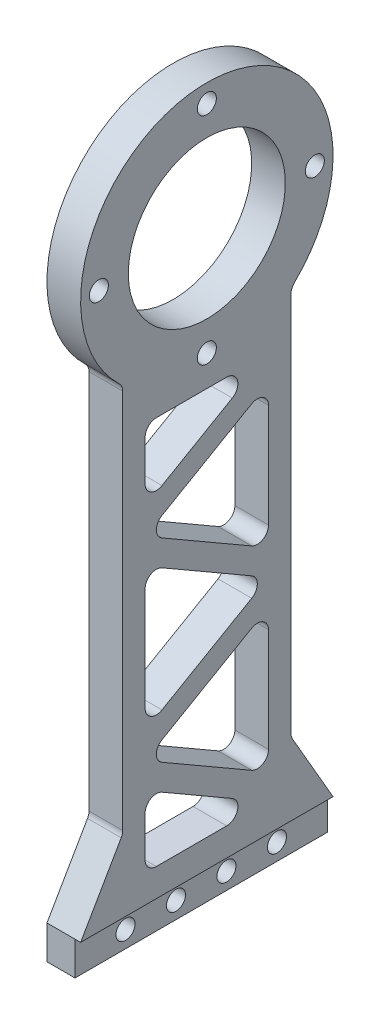
SolidWorks part; units mm, degrees
material "Сплав 2024"
ref_plane "Спереди" through (0, 0, 0) normal (0, 0, 1) x (1, 0, 0)
ref_plane "Сверху" through (0, 0, 0) normal (0, 1, 0) x (1, 0, 0)
ref_plane "Справа" through (0, 0, 0) normal (1, 0, 0) x (0, 0, -1)
sketch "Эскиз1" plane through (0, 0, 0) normal (0, 1, 0) x (1, 0, 0)
  line L1 (0, 0) -> (6, 0)
  line L2 (0, 0) -> (0, -30)
  line L3 (0, -30) -> (6, -30)
  line L4 (6, 0) -> (6, -30)
  dimension "D1" = 6
  dimension "D2" = 30
extrude "Бобышка-Вытянуть1" add sketch "Эскиз1" along normal blind 227
sketch "Эскиз2" plane through (0, 0, 0) normal (-1, 0, 0) x (0, 0, 1)
  line L0 (30, 105) -> (0, 105) construction
  line L3 (15, 227) -> (15, 0) construction
  line L4 (0, 227) -> (30, 227) construction
  line L5 (0, 0) -> (30, 0) construction
  line L6 (30, 0) -> (0, 0) construction
  circle A0 centre (15, 105) radius 22.5
  dimension "D1" = 45
  dimension "D2" = 105
extrude "Бобышка-Вытянуть2" add sketch "Эскиз2" against normal up to surface (6 mm away) up to face at (6, 113.5, 15)
sketch "Эскиз3" plane through (0, 0, 0) normal (-1, 0, 0) x (0, 0, 1)
  circle A0 centre (15, 105) radius 14
  dimension "D1" = 28
extrude "Вырез-Вытянуть1" cut sketch "Эскиз3" against normal through all
sketch "Эскиз4" plane through (6, 0, 0) normal (-1, 0, 0) x (0, 0, 1)
  line L0 (15, 127.5) -> (15, 82.5) construction
  line L1 (15, 227) -> (15, 0) construction
  line L2 (37.5, 105) -> (-7.5, 105) construction
  circle A0 centre (15, 105) radius 19.25 construction
  circle A1 centre (15, 105) radius 22.5 construction
  dimension "D1" = 38.5
hole_wizard "Отверстие с зазором M32" positions "Эскиз6" profile "Эскиз5" hole size "M3" standard "Ansi Metric" end condition through all
sketch "Эскиз6" plane through (6, -25.0247, 7.2629) normal (-1, 0, 0) x (0, 0, 1)
  line L0 (7.7371, 152.5247) -> (7.7371, 107.5247) construction
  line L1 (30.2371, 130.0247) -> (-14.7629, 130.0247) construction
  circle A0 centre (7.7371, 130.0247) radius 19.25 construction
  point P0 (7.7371, 149.2747)
  point P6 (-11.5129, 130.0247)
  point P10 (7.7371, 110.7747)
  point P12 (26.9871, 130.0247)
sketch "Эскиз5" plane through (6, 124.25, 15) normal (0, 1, 0) x (0, 0, -1)
  line L0 (0, 0) -> (0, 6)
  line L1 (0, 6) -> (1.7, 6)
  line L2 (1.7, 6) -> (1.7, 0)
  line L5 (1.7, 0) -> (0, 0)
  line L11 (0, -6.35) -> (0, 107.95) construction
  dimension "Диаметр сквозного отверстия" = 3.4
  dimension "Глубина сквозного отверстия" = 6
sketch "Эскиз8" plane through (6, 0, 0) normal (1, 0, 0) x (0, 0, -1)
  line L0 (-15, 227) -> (-15, 0) construction
  line L1 (-30, 227) -> (0, 227) construction
  line L2 (-30, 0) -> (0, 0) construction
  line L3 (19.447, 105) -> (-49.447, 105) construction
  line L4 (0, 227) -> (0, 121.7705) construction
  line L5 (-26, 145) -> (-4, 145) construction
  line L6 (-26, 145) -> (-26, 65) construction
  line L7 (-26, 65) -> (-4, 65) construction
  line L8 (-4, 145) -> (-4, 65) construction
  line L9 (-26, 145) -> (-4, 65) construction
  line L10 (-26, 65) -> (-4, 145) construction
  point P8 (-15, 105)
  point P9 (-15, 105)
  dimension "D1" = 4
  dimension "D2" = 80
  dimension "D3" = 105
sketch "Эскиз11" plane through (6, 0, 0) normal (1, 0, 0) x (0, 0, -1)
  line L0 (-30, 0) -> (0, 0) construction
  line L1 (-15, 227) -> (-15, 0) construction
  line L2 (-30, 227) -> (0, 227) construction
  line L3 (0, 88.2295) -> (0, 0) construction
  line L4 (-30, 88.2295) -> (-30, 0) construction
  line L5 (-37.5, 3) -> (7.5, 3) construction
  line L20 (-1.5, 0) -> (-1.5, 6) construction
  line L21 (-10.5, 0) -> (-10.5, 6) construction
  line L22 (-19.5, 0) -> (-19.5, 6) construction
  line L23 (-28.5, 0) -> (-28.5, 6) construction
  line L25 (-37.5, 0) -> (7.5, 6) construction
  line L26 (-37.5, 6) -> (7.5, 0) construction
  line L27 (-37.5, 6) -> (7.5, 6) construction
  line L28 (0, 18.9904) -> (7.5, 6)
  line L29 (-30, 18.9904) -> (0, 18.9904)
  line L30 (7.5, 6) -> (7.5, 0)
  line L31 (-37.5, 0) -> (7.5, 0)
  line L32 (-37.5, 6) -> (-37.5, 0)
  line L33 (-37.5, 6) -> (-30, 18.9904)
  point P2 (-15, 3)
  dimension "D1" = 45
  dimension "D2" = 6
  dimension "D3" = 9
  dimension "D4" = 9
  dimension "D5" = 9
  dimension "D6" = 9
  dimension "D7" = 120
extrude "Бобышка-Вытянуть3" add sketch "Эскиз11" against normal up to surface (6 mm away) up to face at (0, 124.25, 13.3)
hole_wizard "Отверстие с зазором M31" positions "Эскиз13" profile "Эскиз12" hole size "M3" standard "Ansi Metric" end condition through all
sketch "Эскиз13" plane through (6, 0, 0) normal (1, 0, 0) x (0, 0, -1)
  line L4 (-28.5, 0) -> (-28.5, 6) construction
  line L5 (-19.5, 0) -> (-19.5, 6) construction
  line L6 (-10.5, 0) -> (-10.5, 6) construction
  line L7 (-1.5, 0) -> (-1.5, 6) construction
  point P16 (-28.5, 3)
  point P20 (-19.5, 3)
  point P24 (-10.5, 3)
  point P28 (-1.5, 3)
sketch "Эскиз12" plane through (6, 3, 28.5) normal (0, 1, 0) x (0, 0, -1)
  line L0 (0, 0) -> (0, 6)
  line L1 (0, 6) -> (1.7, 6)
  line L2 (1.7, 6) -> (1.7, 0)
  line L5 (1.7, 0) -> (0, 0)
  line L11 (0, -6.35) -> (0, 107.95) construction
  dimension "Диаметр сквозного отверстия" = 3.4
  dimension "Глубина сквозного отверстия" = 6
sketch "Эскиз14" plane through (6, 0, 0) normal (1, 0, 0) x (0, 0, -1)
  line L5 (-37.5, 0) -> (7.5, 0)
  line L6 (-37.5, 0) -> (-37.5, 6)
  line L7 (-37.5, 6) -> (7.5, 6)
  line L8 (7.5, 0) -> (7.5, 6)
extrude "Вырез-Вытянуть2" cut sketch "Эскиз14" against normal blind 1
sketch "Эскиз15" plane through (6, 0, 0) normal (1, 0, 0) x (0, 0, -1)
  line L0 (0, 227) -> (0, 121.7705) construction
  line L1 (-30, 227) -> (0, 227)
  line L2 (-30, 227) -> (-30, 121.7705)
  line L4 (0, 227) -> (0, 121.7705)
  arc A1 (-30, 121.7705) -> (0, 121.7705) centre (-15, 105) cw
extrude "Вырез-Вытянуть3" cut sketch "Эскиз15" against normal up to surface (6 mm away) up to face at (0, 3, 26.8)
sketch "Эскиз16" plane through (6, 0, 0) normal (1, 0, 0) x (0, 0, -1)
  line L0 (-26, 0) -> (-26, 89.3005) construction
  line L1 (-37.5, 0) -> (7.5, 0) construction
  line L2 (-4, 0) -> (-4, 89.3005) construction
  line L3 (-30, 88.2295) -> (-30, 18.9904) construction
  line L4 (0, 88.2295) -> (0, 18.9904) construction
  line L5 (-30, 80.25) -> (0, 80.25) construction
  line L6 (-26, 80.25) -> (-4, 80.25)
  line L7 (-4, 80.25) -> (-26, 67.5483)
  line L8 (-26, 67.5483) -> (-26, 80.25)
  line L9 (-26, 62.9295) -> (-4, 75.6312)
  line L10 (-4, 75.6312) -> (-4, 50.2278)
  line L11 (-4, 50.2278) -> (-26, 62.9295)
  line L12 (-26, 58.3107) -> (-4, 45.609)
  line L13 (-4, 45.609) -> (-26, 32.9073)
  line L14 (-26, 32.9073) -> (-26, 58.3107)
  line L15 (-26, 28.2885) -> (-4, 40.9902)
  line L16 (-4, 40.9902) -> (-4, 15.5868)
  line L17 (-4, 15.5868) -> (-26, 28.2885)
  line L18 (-26, 23.6697) -> (-4, 10.968)
  line L19 (-4, 10.968) -> (-26, 10.968)
  line L20 (-26, 10.968) -> (-26, 23.6697)
  circle A2 centre (-15, 85.75) radius 1.7 construction
  dimension "D3" = 5.5
  dimension "D1" = 4
  dimension "D2" = 4
  dimension "D4" = 30
  dimension "D5" = 4
  dimension "D6" = 4
  dimension "D7" = 4
  dimension "D8" = 4
  dimension "D9" = 60
  dimension "D10" = 60
  dimension "D11" = 60
extrude "Вырез-Вытянуть4" cut sketch "Эскиз16" against normal through all
fillet "Скругление1" radius 2 19 edges at (3, 18.9904, 30) (3, 18.9904, 0) (3, 10.968, 26) (3, 23.6697, 26) (3, 10.968, 4) (3, 15.5868, 4) (3, 40.9902, 4) (3, 28.2885, 26) (3, 32.9073, 26) (3, 58.3107, 26) (3, 45.609, 4) (3, 50.2278, 4) (3, 62.9295, 26) (3, 75.6312, 4) (3, 80.25, 4) (3, 67.5483, 26) (3, 80.25, 26) (3, 88.2295, 30) (3, 88.2295, 0)
chamfer "Фаска1" [suppressed] distance 1 angle 45
equation "\"D4@Эскиз11\"=\"D3@Эскиз11\""
equation "\"D5@Эскиз11\"=\"D3@Эскиз11\""
equation "\"D6@Эскиз11\"=\"D4@Эскиз11\""
equation "\"D3@Эскиз11\" = \"D1@Эскиз11\" / 5"
equation "\"D10@Эскиз16\"=\"D4@Эскиз16\"*2"
equation "\"D9@Эскиз16\"=\"D10@Эскиз16\""
equation "\"D11@Эскиз16\"=\"D10@Эскиз16\""
